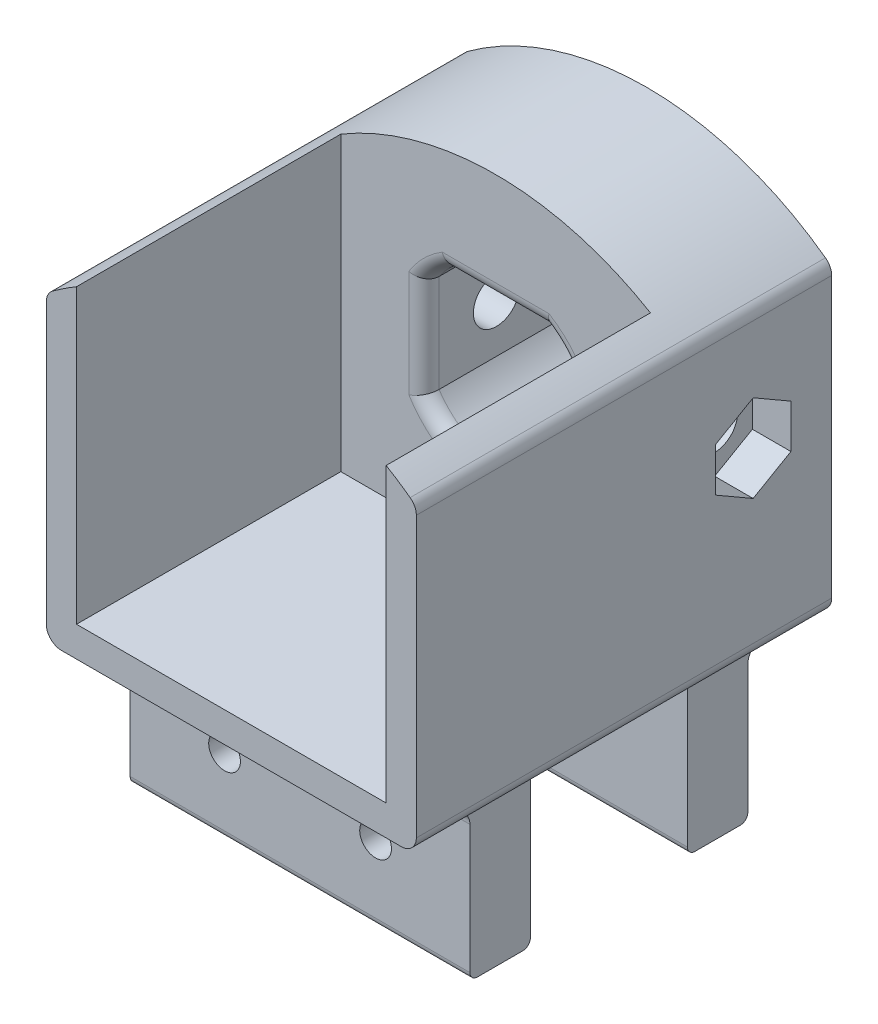
SolidWorks part; units mm, degrees
ref_plane "前视基准面" through (0, 0, 0) normal (0, 0, 1) x (1, 0, 0)
ref_plane "上视基准面" through (0, 0, 0) normal (0, 1, 0) x (1, 0, 0)
ref_plane "右视基准面" through (0, 0, 0) normal (1, 0, 0) x (0, 0, -1)
sketch "草图1" plane through (0, 0, 0) normal (0, 0, 1) x (1, 0, 0)
  line L0 (-24.5, -24.4) -> (24.5, -24.4)
  line L1 (-6.4807, 9.5) -> (6.4807, 9.5)
  line L2 (-9.5, 6.4807) -> (-9.5, -6.4807)
  line L3 (-6.4807, -9.5) -> (6.4807, -9.5)
  line L4 (9.5, 6.4807) -> (9.5, -6.4807)
  line L5 (-8.1317, 8.1317) -> (8.1317, -8.1317) construction
  line L6 (-8.1317, -8.1317) -> (8.1317, 8.1317) construction
  line L7 (0, 0) -> (0, -9.5) construction
  line L8 (-24.5, -24.4) -> (-24.5, 15.6)
  line L9 (24.5, -24.4) -> (24.5, 15.6)
  line L10 (9.5, 0) -> (-9.5, 0) construction
  line L11 (0, -9.5) -> (0, 9.5) construction
  arc A0 (6.4807, -9.5) -> (9.5, -6.4807) centre (0, 0) ccw
  arc A1 (-6.4807, 9.5) -> (-9.5, 6.4807) centre (0, 0) ccw
  arc A2 (9.5, 6.4807) -> (6.4807, 9.5) centre (0, 0) ccw
  arc A3 (-9.5, -6.4807) -> (-6.4807, -9.5) centre (0, 0) ccw
  arc A4 (24.5, 15.6) -> (-24.5, 15.6) centre (0, -16.2321) ccw
  point P0 (0, 0)
  point P17 (0, -24.4)
  dimension "D3" = 23
  dimension "D6" = 19
  dimension "D2" = 24.4
  dimension "D4" = 49
  dimension "D5" = 40
extrude "凸台-拉伸1" add sketch "草图1" along normal blind 20
sketch "草图2" plane through (0, 0, 20) normal (0, 0, 1) x (1, 0, 0)
  line L6 (-20.5, 13.5661) -> (-20.5, -20.4)
  line L7 (-20.5, -20.4) -> (20.5, -20.4)
  line L8 (20.5, -20.4) -> (20.5, 13.5661)
  line L9 (-20.5, 18.3118) -> (-20.5, -20.4)
  line L10 (-20.5, -20.4) -> (20.5, -20.4)
  line L11 (20.5, -20.4) -> (20.5, 18.3118)
  line L12 (-24.5, 15.6) -> (-24.5, -24.4)
  line L13 (-24.5, -24.4) -> (24.5, -24.4)
  line L14 (24.5, -24.4) -> (24.5, 15.6)
  line L15 (-24.5, 15.6) -> (-24.5, -24.4)
  line L16 (-24.5, -24.4) -> (24.5, -24.4)
  line L17 (24.5, -24.4) -> (24.5, 15.6)
  arc A1 (-20.5, 18.3118) -> (-24.5, 15.6) centre (0, -16.2321) ccw
  arc A2 (20.5, 13.5661) -> (-20.5, 13.5661) centre (0, -16.2321) ccw
  arc A4 (24.5, 15.6) -> (-24.5, 15.6) centre (0, -16.2321) ccw
  arc A5 (24.5, 15.6) -> (20.5, 18.3118) centre (0, -16.2321) ccw
  dimension "D2" = 41
  dimension "D3" = 0
  dimension "D1" = 4
extrude "凸台-拉伸2" add sketch "草图2" along normal blind 35
fillet "圆角1" radius 2 4 edges at (24.5, 15.6, 27.5) (-24.5, 15.6, 27.5) (24.5, -24.4, 27.5) (-24.5, -24.4, 27.5)
fillet "圆角2" radius 2 8 edges at (8.1317, 8.1317, 20) (9.5, 0, 20) (8.1317, -8.1317, 20) (0, -9.5, 20) (-8.1317, -8.1317, 20) (0, 9.5, 20) (-8.1317, 8.1317, 20) (-9.5, 0, 20)
sketch "草图3" plane through (-24.5, 0, 0) normal (-1, 0, 0) x (0, 0, 1)
  line L0 (55, 14.5998) -> (55, -22.4) construction
  line L1 (0, 14.5998) -> (55, 14.5998)
  line L2 (0, 14.5998) -> (0, 6.5998)
  line L3 (0, 6.5998) -> (55, 6.5998)
  line L4 (55, 14.5998) -> (55, 6.5998)
  line L5 (0, 14.5998) -> (0, -22.4) construction
  line L6 (55, -22.0002) -> (0, -22.0002)
  line L7 (55, -22.0002) -> (55, -14.0002)
  line L8 (55, -14.0002) -> (0, -14.0002)
  line L9 (0, -22.0002) -> (0, -14.0002)
  dimension "D1" = 8
  dimension "D2" = 20.6
  dimension "D3" = 8
extrude "凸台-拉伸3" add sketch "草图3" along normal blind 20
sketch "草图4" plane through (0, 14.5998, 0) normal (0, 1, 0) x (1, 0, 0)
  line L0 (-34.5, 0) -> (-34.5, -55) construction
  line L1 (-44.5, 0) -> (-24.5, 0) construction
  line L2 (-44.5, -55) -> (-24.5, -55) construction
  line L3 (-40.25, -18.25) -> (-40.25, -36.75) construction
  line L4 (-39.25, -11.75) -> (-29.75, -11.75)
  line L5 (-40.25, -12.75) -> (-40.25, -17.25)
  line L6 (-39.25, -18.25) -> (-29.75, -18.25)
  line L7 (-28.75, -12.75) -> (-28.75, -17.25)
  line L8 (-40.25, -11.75) -> (-28.75, -18.25) construction
  line L9 (-40.25, -18.25) -> (-28.75, -11.75) construction
  line L10 (-39.25, -36.75) -> (-29.75, -36.75)
  line L11 (-40.25, -37.75) -> (-40.25, -42.25)
  line L12 (-39.25, -43.25) -> (-29.75, -43.25)
  line L13 (-28.75, -37.75) -> (-28.75, -42.25)
  line L14 (-40.25, -36.75) -> (-28.75, -43.25) construction
  line L15 (-40.25, -43.25) -> (-28.75, -36.75) construction
  arc A0 (-40.25, -42.25) -> (-39.25, -43.25) centre (-39.25, -42.25) ccw
  arc A1 (-29.75, -43.25) -> (-28.75, -42.25) centre (-29.75, -42.25) ccw
  arc A2 (-29.75, -36.75) -> (-28.75, -37.75) centre (-29.75, -37.75) cw
  arc A3 (-39.25, -36.75) -> (-40.25, -37.75) centre (-39.25, -37.75) ccw
  arc A4 (-40.25, -17.25) -> (-39.25, -18.25) centre (-39.25, -17.25) ccw
  arc A5 (-29.75, -18.25) -> (-28.75, -17.25) centre (-29.75, -17.25) ccw
  arc A6 (-29.75, -11.75) -> (-28.75, -12.75) centre (-29.75, -12.75) cw
  arc A7 (-39.25, -11.75) -> (-40.25, -12.75) centre (-39.25, -12.75) ccw
  point P6 (-34.5, -15)
  point P11 (-34.5, -40)
  point P16 (-40.25, -27.5)
  point P17 (-34.5, -27.5)
  dimension "D4" = 1
  dimension "D1" = 11.5
  dimension "D2" = 6.5
  dimension "D3" = 25
extrude "切除-拉伸1" cut sketch "草图4" against normal through all both and the other way through all
fillet "圆角3" radius 2 4 edges at (-44.5, -22.0002, 27.5) (-44.5, -14.0002, 27.5) (-44.5, 6.5998, 27.5) (-44.5, 14.5998, 27.5)
sketch "草图6" plane through (24.5, 0, 0) normal (1, 0, 0) x (0, 0, -1)
  line L0 (0, -6.4807) -> (0, 6.4807) construction
  line L1 (0, -6.4807) -> (0, 6.4807) construction
  line L2 (0, 0) -> (-55, 0) construction
  line L3 (-55, -22.4) -> (-55, 14.5998) construction
  circle A0 centre (-10.4, 0) radius 3.05
  dimension "D1" = 10.4
  dimension "D2" = 6.1
extrude "切除-拉伸2" cut sketch "草图6" against normal through all both and the other way through all
sketch "草图7" plane through (24.5, 0, 0) normal (1, 0, 0) x (0, 0, -1)
  line L0 (0, -22.4) -> (0, 14.5998) construction
  line L1 (-5.4, -2.8868) -> (-5.4, 2.8868)
  line L2 (-5.4, 2.8868) -> (-10.4, 5.7735)
  line L3 (-10.4, 5.7735) -> (-15.4, 2.8868)
  line L4 (-15.4, 2.8868) -> (-15.4, -2.8868)
  line L5 (-15.4, -2.8868) -> (-10.4, -5.7735)
  line L6 (-10.4, -5.7735) -> (-5.4, -2.8868)
  circle A0 centre (-10.4, 0) radius 5 construction
  dimension "D1" = 10
extrude "切除-拉伸3" cut sketch "草图7" against normal blind 5.1
mirror "镜向1" about plane through (0, 0, 0) normal (1, 0, 0) of "切除-拉伸3", "切除-拉伸1", "凸台-拉伸3", "圆角3"
sketch "草图9" plane through (0, 0, 0) normal (0, 0, -1) x (-1, 0, 0)
  line L0 (-39.25, 14.5998) -> (-29.75, 14.5998) construction
  line L1 (-39.25, 14.5998) -> (-29.75, 14.5998)
  line L2 (-34.5, 14.5998) -> (-34.5, 6.5998) construction
  line L3 (-42.5, 6.5998) -> (-24.5, 6.5998) construction
  line L4 (-34.5, -14.0002) -> (-34.5, -22.0002) construction
  line L5 (-42.5, -14.0002) -> (-24.5, -14.0002) construction
  line L6 (-42.5, -22.0002) -> (-24.5, -22.0002) construction
  line L7 (0, 23.9367) -> (0, 0) construction
  circle A0 centre (-34.5, 10.5998) radius 1.6
  circle A1 centre (-34.5, -18.0002) radius 1.6
  arc A2 (23.679, 16.2154) -> (-23.679, 16.2154) centre (0, -16.2321) ccw construction
  circle A3 centre (34.5, -18.0002) radius 1.6
  circle A4 centre (34.5, 10.5998) radius 1.6
  dimension "D1" = 3.2
extrude "切除-拉伸4" cut sketch "草图9" against normal through all both and the other way through all contours A3 | A4 | A0 | A1 region at (34.5, 10.5998, 0) region at (-34.5, -18.0002, 0) region at (-34.5, 10.5998, 0)
sketch "草图10" plane through (0, 0, 0) normal (0, 0, -1) x (-1, 0, 0)
  circle A0 centre (34.5, 10.5998) radius 3
  circle A1 centre (34.5, -18.0002) radius 3
  circle A2 centre (-34.5, -18.0002) radius 3
  circle A3 centre (-34.5, 10.5998) radius 3
  dimension "D1" = 6
extrude "切除-拉伸5" cut sketch "草图10" against normal blind 3
sketch "草图11" plane through (0, 0, 55) normal (0, 0, 1) x (1, 0, 0)
  circle A0 centre (34.5, 10.5998) radius 3
  circle A1 centre (34.5, -18.0002) radius 3
  circle A2 centre (-34.5, -18.0002) radius 3
  circle A3 centre (-34.5, 10.5998) radius 3
  dimension "D1" = 6
extrude "切除-拉伸6" cut sketch "草图11" against normal blind 2
sketch "草图12" plane through (0, 0, 0) normal (0, 0, -1) x (-1, 0, 0)
  line L0 (42.5, 14.5998) -> (24.5, 14.5998) construction
  line L1 (-24.5, 14.5998) -> (-54.0982, 14.5998)
  line L2 (-24.5, 14.5998) -> (-24.5, -22.6486)
  line L3 (-24.5, -22.6486) -> (-54.0982, -22.6486)
  line L4 (-54.0982, 14.5998) -> (-54.0982, -22.6486)
  line L5 (24.5, 14.5998) -> (55.1542, 14.5998)
  line L6 (24.5, 14.5998) -> (24.5, -26.8727)
  line L7 (24.5, -26.8727) -> (55.1542, -26.8727)
  line L8 (55.1542, 14.5998) -> (55.1542, -26.8727)
  arc A0 (24.5, 14.5998) -> (23.679, 16.2154) centre (22.5, 14.5998) ccw construction
extrude "切除-拉伸7" cut sketch "草图12" against normal through all both and the other way through all
sketch "草图13" plane through (0, -24.4, 0) normal (0, -1, 0) x (1, 0, 0)
  line L0 (-22.5, 55) -> (-22.5, 0) construction
  line L1 (-22.5, 45.9) -> (22.5, 45.9)
  line L2 (-22.5, 45.9) -> (-22.5, 37.9)
  line L3 (-22.5, 37.9) -> (22.5, 37.9)
  line L4 (22.5, 45.9) -> (22.5, 37.9)
  line L5 (22.5, 0) -> (22.5, 55) construction
  line L6 (-22.5, 37.9) -> (-22.5, 17.1) construction
  line L7 (-22.5, 17.1) -> (22.5, 17.1)
  line L8 (-22.5, 17.1) -> (-22.5, 9.1)
  line L9 (-22.5, 9.1) -> (22.5, 9.1)
  line L10 (22.5, 17.1) -> (22.5, 9.1)
  line L11 (-22.5, 27.5) -> (22.5, 27.5) construction
  point P14 (-22.5, 27.5)
  dimension "D1" = 8
  dimension "D2" = 8
  dimension "D3" = 20.8
extrude "凸台-拉伸4" add sketch "草图13" along normal blind 20
sketch "草图14" plane through (0, 0, 45.9) normal (0, 0, 1) x (1, 0, 0)
  line L0 (-22.5, -34.4) -> (22.5, -34.4) construction
  line L1 (-22.5, -44.4) -> (-22.5, -24.4) construction
  line L2 (22.5, -44.4) -> (22.5, -24.4) construction
  line L3 (0, -24.4) -> (0, -44.4) construction
  line L4 (22.5, -24.4) -> (-22.5, -24.4) construction
  line L5 (22.5, -44.4) -> (-22.5, -44.4) construction
  circle A0 centre (-10, -34.4) radius 2.1
  circle A1 centre (10, -34.4) radius 2.1
  dimension "D1" = 20
  dimension "D2" = 4.2
extrude "切除-拉伸8" cut sketch "草图14" against normal through all both and the other way through all
fillet "圆角5" radius 1 4 edges at (0, -44.4, 9.1) (0, -44.4, 17.1) (0, -44.4, 37.9) (0, -44.4, 45.9)
fillet "圆角6" radius 2 2 edges at (0, -24.4, 9.1) (0, -24.4, 45.9)
